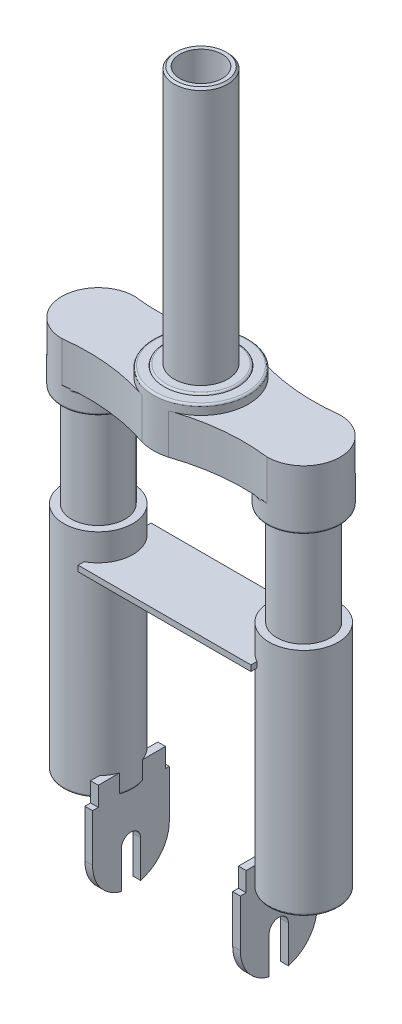
SolidWorks part; units mm, degrees
ref_plane "Front Plane" through (0, 0, 0) normal (0, 0, 1) x (1, 0, 0)
ref_plane "Top Plane" through (0, 0, 0) normal (0, 1, 0) x (1, 0, 0)
ref_plane "Right Plane" through (0, 0, 0) normal (1, 0, 0) x (0, 0, -1)
sketch "Sketch1" plane through (0, 0, 0) normal (0, 0, 1) x (1, 0, 0)
  line L0 (0, -70) -> (0, 70)
  point P4 (0, 0)
  dimension "D1" = 140
sketch "Sketch2" plane through (0, 0, 0) normal (0, 1, 0) x (1, 0, 0)
  circle A0 centre (0, 0) radius 14
  circle A1 centre (0, 0) radius 11
  dimension "D1" = 28
  dimension "D2" = 3
extrude "Boss-Extrude1" add sketch "Sketch2" against normal blind 140
sketch "Sketch3" plane through (0, -140, 0) normal (0, -1, 0) x (1, 0, 0)
  line L0 (-53.5, 0) -> (53.5, 0) construction
  line L5 (-72.5, 24.75) -> (72.5, -24.75) construction
  line L6 (-72.5, -24.75) -> (72.5, 24.75) construction
  line L7 (0, 58.8886) -> (0, -34.6433) construction
  circle A1 centre (0, 0) radius 17.2
  arc A2 (49.4574, -18.5649) -> (49.4574, 18.5649) centre (53.5, 0) ccw
  arc A3 (-49.4574, -18.5649) -> (-49.4574, 18.5649) centre (-53.5, 0) cw
  arc A4 (-8.7282, -23.1599) -> (8.7282, -23.1599) centre (0, 0) ccw
  arc A5 (-53.5, -19) -> (-6.9022, -23.7681) centre (-40.4353, -121.401) cw
  arc A6 (53.5, -19) -> (6.9022, -23.7681) centre (40.4353, -121.401) ccw
  arc A7 (53.5, 19) -> (6.9022, 23.7681) centre (40.4353, 121.401) cw
  arc A8 (-53.5, 19) -> (-6.9022, 23.7681) centre (-40.4353, 121.401) ccw
  arc A9 (8.7282, 23.1599) -> (-8.7282, 23.1599) centre (0, 0) ccw
  circle A10 centre (0, 0) radius 11 construction
  point P0 (0, 0)
  point P12 (0, 0)
  dimension "D1" = 103.231
  dimension "D3" = 34.4
  dimension "D4" = 38
  dimension "D5" = 49.5
  dimension "D2" = 6.9022
  dimension "D6" = 8.7282
  dimension "D7" = 72.5
  dimension "D8" = 24.75
  dimension "D9" = 93.5319
  dimension "D10" = 58.8886
extrude "Boss-Extrude4" add sketch "Sketch3" along normal blind 21 separate body contours A7 A9 A8 A3 A5 A4 A6 A2 A1 region at (28.6907, -140, -17.2982)
sketch "Sketch7" plane through (0, -140, 0) normal (0, 1, 0) x (1, 0, 0)
  circle A0 centre (0, 0) radius 24.75
  dimension "D1" = 49.5
extrude "Boss-Extrude5" add sketch "Sketch7" along normal blind 5
fillet "Fillet3" radius 1 1 edges at (0, -135, 24.75)
sketch "Sketch8" plane through (0, -135, 0) normal (0, 1, 0) x (1, 0, 0)
  circle A0 centre (0, 0) radius 19.15
  circle A1 centre (0, 0) radius 14 construction
  circle A2 centre (0, 0) radius 14
  dimension "D1" = 38.3
extrude "Boss-Extrude6" add sketch "Sketch8" along normal blind 0.9
fillet "Fillet4" radius 1 1 edges at (0, -134.1, 19.15)
sketch "Sketch9" plane through (0, -161, 0) normal (0, -1, 0) x (1, 0, 0)
  line L0 (-72.5, 0) -> (-53.5, 0) construction
  line L1 (0, 31.6889) -> (0, -24.75) construction
  arc A0 (-53.5, 19) -> (-53.5, -19) centre (-53.5, 0) ccw construction
  circle A1 centre (-53.5, 0) radius 19
  arc A2 (-6.9022, -23.7681) -> (6.9022, -23.7681) centre (0, 0) ccw construction
  circle A3 centre (53.5, 0) radius 19
  dimension "D1" = 38
extrude "Boss-Extrude7" add sketch "Sketch9" along normal blind 10
fillet "Fillet5" radius 1 4 edges at (34.5, -161, 0) (53.5, -171, 19) (-34.5, -161, 0) (-53.5, -171, -19)
chamfer "Chamfer1" distance 1 angle 45 1 edges at (0, 0, 14)
sketch "Sketch10" plane through (0, -171, 0) normal (0, -1, 0) x (1, 0, 0)
  line L0 (0, 39.8113) -> (0, -36.7225) construction
  circle A0 centre (-53.5, 0) radius 18 construction
  circle A1 centre (-53.5, 0) radius 18 construction
  circle A2 centre (-53.5, 0) radius 14
  circle A3 centre (53.5, 0) radius 14
  dimension "D1" = 28
extrude "Boss-Extrude8" add sketch "Sketch10" along normal blind 53
fillet "Fillet7" radius 1 2 edges at (53.5, -171, 14) (-53.5, -171, -14)
sketch "Sketch11" plane through (0, -224, 0) normal (0, -1, 0) x (1, 0, 0)
  line L0 (0, 38.6993) -> (0, -16.4417) construction
  circle A2 centre (-53.5, 0) radius 18
  circle A3 centre (-53.5, 0) radius 14 construction
  circle A4 centre (53.5, 0) radius 18
  dimension "D1" = 36
extrude "Boss-Extrude9" add sketch "Sketch11" along normal blind 120
fillet "Fillet8" radius 1 2 edges at (53.5, -344, 18) (-53.5, -344, -18)
sketch "Sketch17" plane through (0, 0, 0) normal (0, 0, 1) x (1, 0, 0)
  line L0 (-53.5, -344) -> (53.5, -344) construction
  line L1 (-70.5, -344) -> (-36.5, -344) construction
  line L2 (36.5, -344) -> (70.5, -344) construction
  line L3 (0, -344) -> (0, -319.3084) construction
  line L4 (0, -344) -> (0, -352.1369) construction
  line L5 (-36.5, -352.1369) -> (36.5, -352.1369) construction
  line L6 (36.5, -352.1369) -> (36.5, -330.8903) construction
  line L7 (-36.5, -344) -> (-36.5, -334) construction
  line L8 (-36.5, -352.1369) -> (-36.5, -337.5926)
  point P13 (0, -352.1369)
  dimension "D1" = 73
ref_plane "Plane1" through (36.5, 0, 0) normal (1, 0, 0) x (0, 0, -1)
sketch "Sketch13" plane through (36.5, 0, 0) normal (1, 0, 0) x (0, 0, -1)
  line L1 (-17, -344) -> (-17, -334) construction
  line L6 (-17, -334) -> (18, -334)
  line L17 (-17, -334) -> (18, -334) construction
  line L18 (18, -343) -> (18, -224) construction
  line L19 (-17, -344) -> (-17, -334)
  line L20 (18, -334) -> (18, -344)
  line L21 (-20, -344) -> (-17, -344)
  line L23 (-20, -344) -> (-20, -368.6338)
  line L24 (0, -344) -> (0, -388.6338) construction
  line L25 (20, -344) -> (20, -368.6338)
  line L26 (-5, -368.6338) -> (-5, -387.9988)
  line L27 (5, -368.6338) -> (5, -387.9988)
  line L28 (18, -344) -> (20, -344)
  arc A3 (5, -387.9988) -> (20, -368.6338) centre (0, -368.6338) ccw
  arc A4 (5, -368.6338) -> (-5, -368.6338) centre (0, -368.6338) ccw
  arc A5 (-20, -368.6338) -> (-5, -387.9988) centre (0, -368.6338) ccw
  point P28 (0, -344)
  dimension "D6" = 10
  dimension "D3" = 368.6338
  dimension "D2" = 20
  dimension "D1" = 10
extrude "Boss-Extrude14" add sketch "Sketch13" along normal blind 4
mirror "Mirror4" about plane through (0, 0, 0) normal (1, 0, 0) of "Boss-Extrude14"
sketch "Sketch20" plane through (0, 0, 0) normal (0, 0, 1) x (1, 0, 0)
  line L0 (-36.5, -387.9988) -> (0, -387.9988) construction
  line L1 (0, -387.9988) -> (0, -237.9988) construction
  line L2 (-45, -237.9988) -> (45, -237.9988)
  line L3 (-45, -237.9988) -> (-45, -240.9988)
  line L4 (45, -237.9988) -> (45, -240.9988)
  line L5 (-45, -240.9988) -> (45, -240.9988)
  point P8 (0, -237.9988)
  dimension "D1" = 150
  dimension "D2" = 90
  dimension "D3" = 3
  dimension "D4" = 3
extrude "Boss-Extrude15" add sketch "Sketch20" along normal mid plane 38
